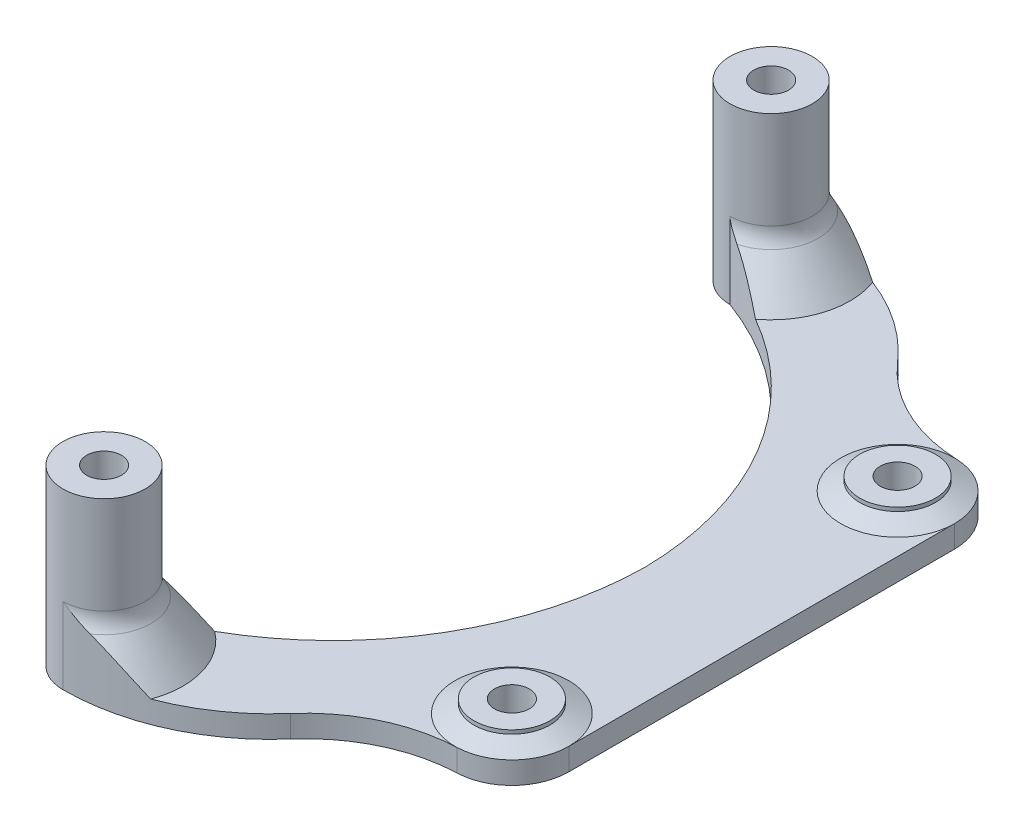
SolidWorks part; units mm, degrees
material "CARBON FIBER TEST"
ref_plane "Front Plane" through (0, 0, 0) normal (0, 0, 1) x (1, 0, 0)
ref_plane "Top Plane" through (0, 0, 0) normal (0, 1, 0) x (1, 0, 0)
ref_plane "Right Plane" through (0, 0, 0) normal (1, 0, 0) x (0, 0, -1)
sketch "Sketch1" plane through (0, 0, 0) normal (0, 1, 0) x (1, 0, 0)
  line L1 (36.375, -26.375) -> (-36.375, -26.375) construction
  line L2 (36.375, -26.375) -> (36.375, 26.375) construction
  line L3 (36.375, 26.375) -> (-36.375, 26.375) construction
  line L4 (-36.375, -26.375) -> (-36.375, 26.375) construction
  line L5 (36.375, -26.375) -> (-36.375, 26.375) construction
  line L6 (36.375, 26.375) -> (-36.375, -26.375) construction
  circle A0 centre (-36.375, 26.375) radius 1.25
  point P0 (0, 0)
  dimension "D3" = 2.5
  dimension "D1" = 72.75
  dimension "D2" = 52.75
sketch "Sketch2" plane through (0, 0, 0) normal (0, 1, 0) x (1, 0, 0)
  line L1 (15.25, -15.25) -> (-15.25, -15.25) construction
  line L2 (15.25, -15.25) -> (15.25, 15.25) construction
  line L3 (15.25, 15.25) -> (-15.25, 15.25) construction
  line L4 (-15.25, -15.25) -> (-15.25, 15.25) construction
  line L5 (15.25, -15.25) -> (-15.25, 15.25) construction
  line L6 (15.25, 15.25) -> (-15.25, -15.25) construction
  circle A0 centre (-15.25, 15.25) radius 1.375
  point P0 (0, 0)
  dimension "D2" = 2.75
  dimension "D1" = 30.5
sketch "Sketch3" plane through (0, 0, 0) normal (0, 1, 0) x (1, 0, 0)
  line L6 (-4.3764, 0) -> (-32.0859, 0) construction
  line L7 (-10.75, 15.25) -> (-10.75, -15.25)
  arc A0 (-36.375, 29.625) -> (-36.375, 23.125) centre (-36.375, 26.375) ccw
  circle A5 centre (-36.375, 26.375) radius 1.375
  circle A6 centre (-15.25, 15.25) radius 1.375
  circle A7 centre (-15.25, -15.25) radius 1.375
  circle A8 centre (-36.375, -26.375) radius 1.375
  arc A10 (-36.375, 23.125) -> (-20.001, 0) centre (-44.9987, -0.3405) cw
  arc A12 (-36.375, 29.625) -> (-24, 24) centre (-36.375, 13.2) cw
  arc A13 (-24, 24) -> (-15.0839, 19.7469) centre (-14.6246, 32.1822) ccw
  arc A14 (-10.75, 15.25) -> (-15.0839, 19.7469) centre (-15.25, 15.25) ccw
  arc A15 (-10.75, -15.25) -> (-15.0839, -19.7469) centre (-15.25, -15.25) cw
  arc A16 (-24, -24) -> (-15.0839, -19.7469) centre (-14.6246, -32.1822) cw
  arc A17 (-36.375, -29.625) -> (-24, -24) centre (-36.375, -13.2) ccw
  arc A18 (-36.375, -29.625) -> (-36.375, -23.125) centre (-36.375, -26.375) cw
  arc A19 (-36.375, -23.125) -> (-20.001, 0) centre (-44.9987, 0.3405) ccw
  point P19 (-10.75, 0)
  dimension "D1" = 6.5
  dimension "D2" = 9
  dimension "D3" = 45
  dimension "D4" = 2.75
  dimension "D5" = 24
  dimension "D7" = 25
  dimension "D6" = 24
extrude "Boss-Extrude1" add sketch "Sketch3" along normal blind 1.75
sketch "Sketch4" plane through (0, 1.75, 0) normal (0, 1, 0) x (1, 0, 0)
  circle A0 centre (-36.375, 26.375) radius 3.25
  circle A1 centre (-36.375, 26.375) radius 1.375
  circle A2 centre (-36.375, -26.375) radius 3.25
  circle A3 centre (-36.375, -26.375) radius 1.375
  dimension "D1" = 6.5
  dimension "D2" = 2.75
extrude "Boss-Extrude2" add sketch "Sketch4" along normal blind 12
sketch "Sketch5" plane through (0, 1.75, 0) normal (0, 1, 0) x (1, 0, 0)
  circle A2 centre (-15.25, 15.25) radius 3
  circle A3 centre (-15.25, 15.25) radius 1.375
  circle A4 centre (-15.25, 15.25) radius 1.375 construction
  circle A5 centre (-15.25, -15.25) radius 1.375
  circle A6 centre (-15.25, -15.25) radius 3
  dimension "D1" = 6
extrude "Boss-Extrude3" add sketch "Sketch5" along normal blind 1
chamfer "Chamfer5" distance 1.5 angle 25 2 edges at (-15.25, 1.75, 12.25) (-15.25, 1.75, -18.25) first distance on face at (-15.25, 1.75, 12.25)
chamfer "Chamfer6" distance 3 angle 50 2 edges at (-33.125, 1.75, 26.375) (-33.125, 1.75, -26.375) first distance on face at (-23.8447, 1.75, 0)
fillet "Fillet5" radius 2 2 edges at (-33.125, 5.3253, -26.375) (-33.125, 5.3253, 26.375)
